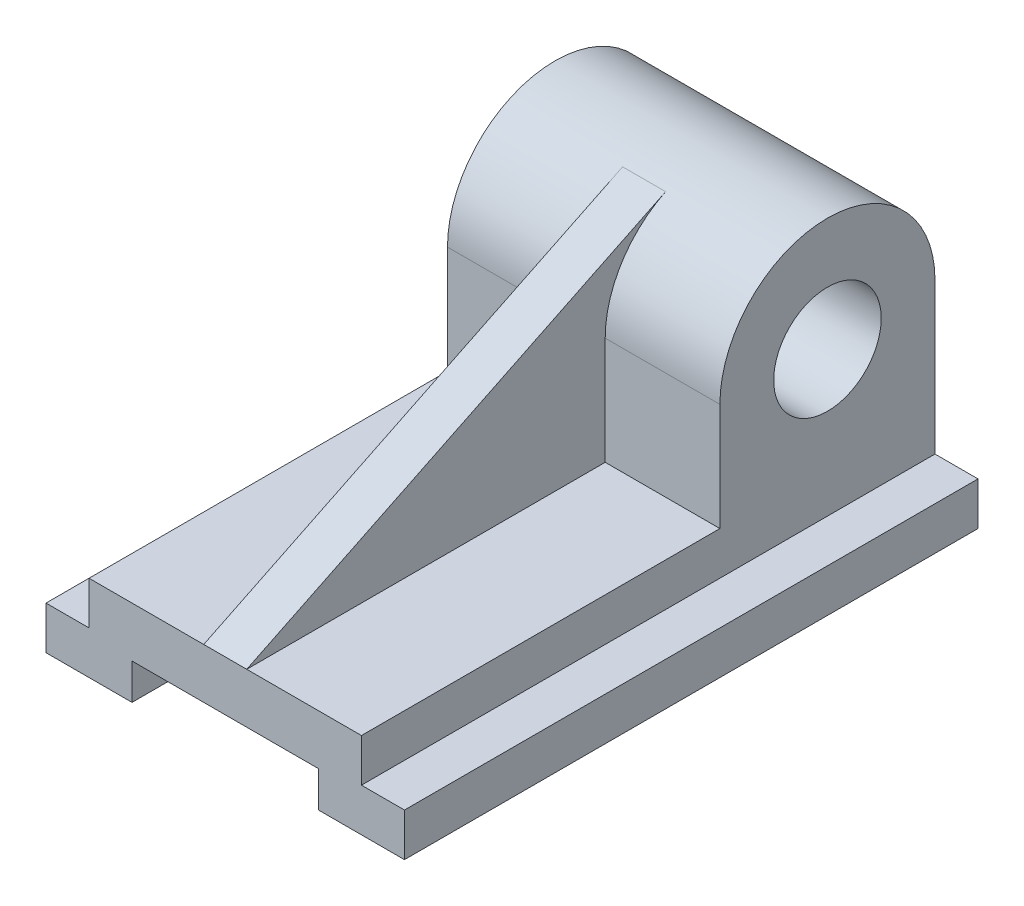
SolidWorks part; units mm, degrees
ref_plane "Front Plane" through (0, 0, 0) normal (0, 0, 1) x (1, 0, 0)
ref_plane "Top Plane" through (0, 0, 0) normal (0, 1, 0) x (1, 0, 0)
ref_plane "Right Plane" through (0, 0, 0) normal (1, 0, 0) x (0, 0, -1)
sketch "Sketch3" plane through (0, 0, 0) normal (0, 0, 1) x (1, 0, 0)
  line L1 (-50, 12) -> (50, 12)
  line L2 (-50, 12) -> (-50, -12)
  line L3 (-50, -12) -> (50, -12)
  line L4 (50, 12) -> (50, -12)
  line L5 (-50, 12) -> (50, -12) construction
  line L6 (-50, -12) -> (50, 12) construction
  point P0 (0, 0)
  dimension "D1" = 100
  dimension "D2" = 24
extrude "Boss-Extrude4" add sketch "Sketch3" along normal blind 160
sketch "Sketch4" plane through (0, 0, 160) normal (0, 0, 1) x (1, 0, 0)
  line L0 (-50, -12) -> (50, -12) construction
  line L1 (-26, -12) -> (26, -12)
  line L2 (-26, -12) -> (-26, -2)
  line L3 (-26, -2) -> (26, -2)
  line L4 (26, -12) -> (26, -2)
  line L5 (-50, 12) -> (-50, -12) construction
  line L6 (50, -12) -> (50, 12) construction
  line L8 (-50, 12) -> (-38, 12)
  line L9 (-50, 12) -> (-50, 0)
  line L10 (-50, 0) -> (-38, 0)
  line L11 (-38, 12) -> (-38, 0)
  line L12 (50, 12) -> (38, 12)
  line L13 (50, 12) -> (50, 0)
  line L14 (50, 0) -> (38, 0)
  line L15 (38, 12) -> (38, 0)
  dimension "D1" = 10
  dimension "D2" = 24
  dimension "D3" = 24
  dimension "D4" = 12
  dimension "D5" = 12
  dimension "D6" = 12
  dimension "D7" = 12
extrude "Cut-Extrude6" cut sketch "Sketch4" against normal through all
sketch "Sketch6" plane through (0, 12, 0) normal (0, 1, 0) x (1, 0, 0)
  line L0 (38, 0) -> (38, -160) construction
  line L1 (-38, 0) -> (38, 0)
  line L2 (-38, 0) -> (-38, -60)
  line L3 (-38, -60) -> (38, -60)
  line L4 (38, 0) -> (38, -60)
  dimension "D1" = 60
extrude "Boss-Extrude6" add sketch "Sketch6" along normal blind 60
fillet "Fillet1" 2 edges at (0, 72, 60) (0, 72, 0) type full round first side face at (0, 42, 60) second side face at (0, 7.6667, 0) middle face at (0, 72, 30)
sketch "Sketch7" plane through (38, 0, 0) normal (1, 0, 0) x (0, 0, -1)
  line L0 (0, 42) -> (0, 0) construction
  circle A0 centre (-30, 40.3235) radius 15
  dimension "D1" = 30
  dimension "D2" = 30
extrude "Cut-Extrude7" cut sketch "Sketch7" against normal through all
sketch "Sketch10" plane through (0, 0, 0) normal (1, 0, 0) x (0, 0, -1)
  line L0 (-160, 12) -> (-43.1461, 68.9663)
  arc A0 (0, 42) -> (-60, 42) centre (-30, 42) ccw construction
rib "Rib4" sketch "Sketch10" sketch "Sketch10" thickness 12 extrusion direction parallel to sketch draft on no parameters "D1"=12
